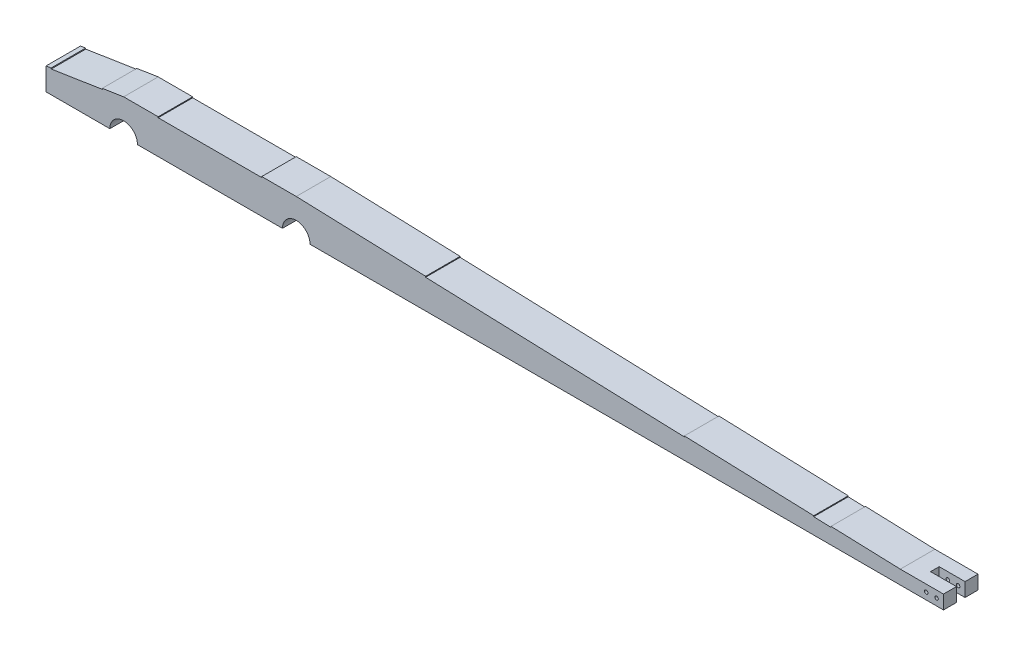
SolidWorks part; units mm, degrees
ref_plane "Plan de face" through (0, 0, 0) normal (0, 0, 1) x (1, 0, 0)
ref_plane "Plan de dessus" through (0, 0, 0) normal (0, 1, 0) x (1, 0, 0)
ref_plane "Plan de droite" through (0, 0, 0) normal (1, 0, 0) x (0, 0, -1)
sketch "Sketch1" plane through (0, 0, 0) normal (0, 0, 1) x (1, 0, 0)
  line L0 (-8, 0) -> (-92, 0)
  line L1 (8, 0) -> (375, 0)
  line L2 (-108, 0) -> (-145, 0)
  line L3 (-100, 20) -> (0, 20)
  line L4 (0, 20) -> (350, 8)
  line L6 (-100, 20) -> (-145, 13)
  line L7 (-145, 0) -> (-145, 13)
  line L8 (350, 8) -> (375, 8)
  line L9 (375, 8) -> (375, 0)
  line L15 (-100, 0) -> (-100, 48.6354) construction
  line L16 (0, 0) -> (0, 46.3997) construction
  arc A0 (8, 0) -> (-8, 0) centre (0, 0) ccw
  arc A1 (-92, 0) -> (-108, 0) centre (-100, 0) ccw
  dimension "D6" = 8
  dimension "D7" = 520
  dimension "D11" = 8
  dimension "D1" = 100
  dimension "D2" = 45
  dimension "D4" = 8
  dimension "D5" = 20
  dimension "D9" = 7
  dimension "D12" = 350
extrude "Boss-Extrude1" add sketch "Sketch1" along normal blind 20
sketch "Sketch2" plane through (0.6849, 19.9765, 0) normal (0.0343, 0.9994, 0) x (0.9994, -0.0343, 0)
  line L0 (349.5203, 0) -> (-0.6853, 0) construction
  line L1 (74.3147, 0) -> (224.3147, 0)
  line L2 (74.3147, 0) -> (74.3147, -20)
  line L3 (74.3147, -20) -> (224.3147, -20)
  line L4 (224.3147, 0) -> (224.3147, -20)
  line L5 (349.5203, -20) -> (-0.6853, -20) construction
  line L6 (-0.6853, -20) -> (-0.6853, 0) construction
  line L8 (299.3147, 0) -> (309.3147, 0)
  line L9 (299.3147, 0) -> (299.3147, -20)
  line L10 (299.3147, -20) -> (309.3147, -20)
  line L11 (309.3147, 0) -> (309.3147, -20)
  dimension "D1" = 150
  dimension "D2" = 75
  dimension "D3" = 10
  dimension "D4" = 75
extrude "RopeGroove1" cut sketch "Sketch2" against normal blind 0.5
sketch "Sketch4" plane through (0, 20, 0) normal (0, 1, 0) x (1, 0, 0)
  line L0 (0, 0) -> (-100, 0) construction
  line L1 (-80, 0) -> (-20, 0)
  line L2 (-80, 0) -> (-80, -20)
  line L3 (-80, -20) -> (-20, -20)
  line L4 (-20, 0) -> (-20, -20)
  line L5 (0, -20) -> (-100, -20) construction
  line L6 (-50, -20) -> (-50, 0) construction
  point P10 (-50, -20)
  dimension "D1" = 60
extrude "RopeGroove2" cut sketch "Sketch4" against normal blind 0.5
sketch "Sketch5" plane through (-5.4002, 34.7155, 0) normal (-0.1537, 0.9881, 0) x (0.9881, 0.1537, 0)
  line L0 (-95.7375, 0) -> (-141.2787, 0) construction
  line L1 (-138.2787, 0) -> (-108.2787, 0)
  line L2 (-138.2787, 0) -> (-138.2787, -20)
  line L3 (-138.2787, -20) -> (-108.2787, -20)
  line L4 (-108.2787, 0) -> (-108.2787, -20)
  line L5 (-95.7375, -20) -> (-141.2787, -20) construction
  line L7 (-141.2787, -20) -> (-141.2787, 0) construction
  dimension "D1" = 30
  dimension "D2" = 3
extrude "RopeGroove3" cut sketch "Sketch5" against normal blind 0.5
sketch "Sketch6" plane through (0, 8, 0) normal (0, 1, 0) x (1, 0, 0)
  line L0 (375, -20) -> (375, 0) construction
  line L1 (360, -12.5) -> (375, -12.5)
  line L2 (360, -12.5) -> (360, -7.5)
  line L3 (360, -7.5) -> (375, -7.5)
  line L4 (375, -12.5) -> (375, -7.5)
  line L5 (360, -12.5) -> (375, -7.5) construction
  line L6 (360, -7.5) -> (375, -12.5) construction
  line L7 (350, -10) -> (375, -10) construction
  line L8 (350, -20) -> (350, 0) construction
  point P0 (367.5, -10)
  dimension "D1" = 5
  dimension "D2" = 15
extrude "Cut-Extrude1" cut sketch "Sketch6" against normal through all
sketch "Sketch7" plane through (0, 0, 20) normal (0, 0, 1) x (1, 0, 0)
  line L0 (375, 4) -> (360, 4) construction
  line L1 (375, 0) -> (375, 8) construction
  line L2 (360, 0) -> (360, 8) construction
  line L3 (360, 0) -> (360, 8)
  circle A0 centre (371, 4) radius 1
  circle A1 centre (365, 4) radius 1
  dimension "D1" = 2
  dimension "D2" = 2
  dimension "D3" = 4
  dimension "D4" = 5
extrude "Cut-Extrude2" cut sketch "Sketch7" against normal through all contours A1 L0 | L0 A1 | L0 A0 | A0 L0 region at (371, 3.5756, 20) region at (371, 4.4244, 20) region at (365, 3.5756, 20) region at (365, 4.4244, 20)
